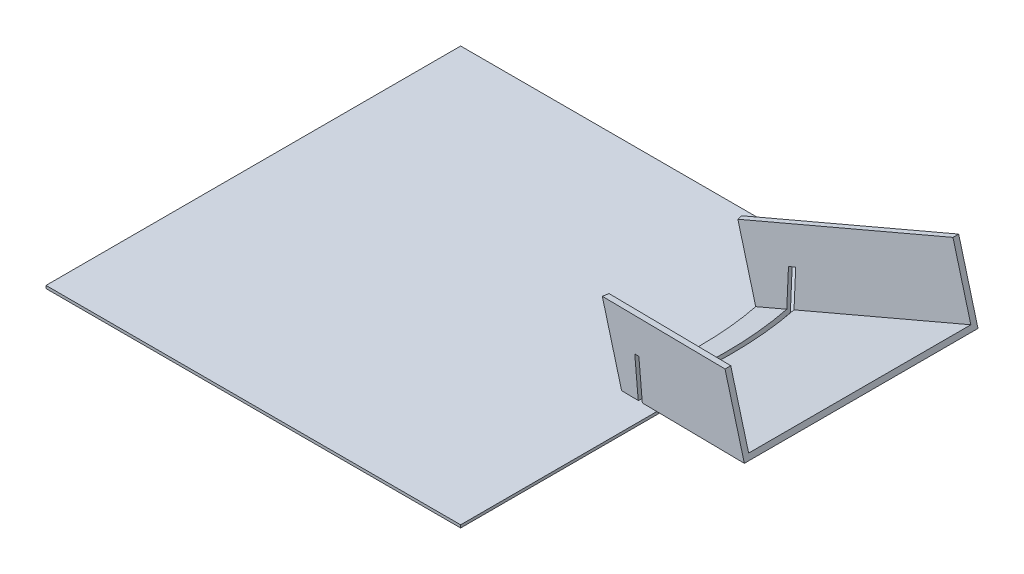
SolidWorks part; units mm, degrees
ref_plane "Front Plane" through (0, 0, 0) normal (0, 0, 1) x (1, 0, 0)
ref_plane "Top Plane" through (0, 0, 0) normal (0, 1, 0) x (1, 0, 0)
ref_plane "Right Plane" through (0, 0, 0) normal (1, 0, 0) x (0, 0, -1)
sketch "Sketch4" plane through (0, 0, 0) normal (0, 1, 0) x (1, 0, 0)
  line L1 (-75, 75) -> (75, 75)
  line L2 (-75, 75) -> (-75, -75)
  line L3 (-75, -75) -> (75, -75)
  line L4 (75, 75) -> (75, -75)
  point P4 (0, 75)
  point P6 (75, 0)
  dimension "D1" = 150
extrude "Boss-Extrude4" add sketch "Sketch4" along normal blind 1
ref_axis "Axis1" through (0, 0, -88.99) along (0, 0, 1)
ref_plane "Plane1" through (0, 0, 0) normal (0.2588, -0.9659, 0) x (0, 0, 1)
sketch "Sketch1" plane through (0, 0, 0) normal (-0.2588, 0.9659, 0) x (0.9659, 0.2588, 0)
  line L0 (0, 0) -> (150, 40.1924)
  line L1 (150, 40.1924) -> (150, -40.1924)
  line L2 (150, -40.1924) -> (0, 0)
  line L3 (150, 42.2629) -> (-0.5176, 1.9319)
  line L4 (150, -42.2629) -> (-0.5176, -1.9319)
  line L5 (-0.5176, 1.9319) -> (0, 0)
  line L6 (150, 42.2629) -> (150, 40.1924)
  line L7 (150, -42.2629) -> (150, -40.1924)
  line L8 (-0.5176, -1.9319) -> (0, 0)
  line L9 (57.2453, -78.7624) -> (62.5056, -85.9998) construction
  circle A0 centre (0, 0) radius 90
  circle A3 centre (0, 0) radius 100 construction
  circle A4 centre (0, 0) radius 97.368
  circle A5 centre (0, 0) radius 106.3152
  point P3 (150, 0)
  dimension "D3" = 180
  dimension "D4" = 200
  dimension "D1" = 150
  dimension "D2" = 30
  dimension "D6" = 2
  dimension "D7" = 2
extrude "Boss-Extrude5" add sketch "Sketch1" along normal blind 2 separate body contours A4 L2 A0 L0 | A4 L0 A0 L3 | A5 L0 A4 L3 | A5 L2 A4 L0 | A5 L4 A4 L2 | L4 A5 L2 L7 | L2 A5 L0 L1 | L0 A5 L3 L6 | A4 L4 A0 L2 region at (87.1517, 23.3522, -25.2113) region at (89.5078, 23.9835, 0) region at (87.1517, 23.3522, 25.2113) region at (94.7634, 25.3918, -27.3228) region at (97.3141, 26.0752, 0) region at (94.7634, 25.3918, 27.3228) region at (121.913, 32.6665, -34.8561) region at (124.4606, 33.3491, 0) region at (121.913, 32.6665, 34.8561)
extrude "Boss-Extrude6" add sketch "Sketch1<7>" along normal blind 25 from surface contours L0 A0 L3 L6 | L4 A0 L2 L7 | A4 L0 A0 L3 | A5 L0 A4 L3 | A5 L4 A4 L2 | A4 L4 A0 L2 region at (87.1517, 23.3522, -25.2113) region at (87.1517, 23.3522, 25.2113) region at (94.7634, 25.3918, -27.3228) region at (94.7634, 25.3918, 27.3228) region at (121.913, 32.6665, -34.8561) region at (121.913, 32.6665, 34.8561) starting at face at (114.5227, 32.7568, 0)
sketch "Sketch1<7>" plane through (0, 0, 0) normal (-0.2588, 0.9659, 0) x (0.9659, 0.2588, 0) same geometry as "Sketch1"
sketch "Sketch5" plane through (0, 0, 0) normal (0, 1, 0) x (1, 0, 0)
  circle A0 centre (0, 0) radius 98.9
  circle A1 centre (0, 0) radius 101.1
  dimension "D1" = 197.8
  dimension "D2" = 202.2
ref_axis "Axis4" through (0, 68.148, 0) along (0, -1, 0)
sketch "Sketch8" plane through (0, 0, 0) normal (0.2588, -0.9659, 0) x (-0.9659, -0.2588, 0)
  circle A0 centre (0, 0) radius 98.9
  circle A1 centre (0, 0) radius 101.1
extrude "Cut-Extrude4" cut sketch "Sketch8" along direction (0, -1, 0) on the side against the normal blind 15
equation "\"slope_angle\"= 15deg"
equation "\"wall_angle\"= 30deg"
equation "\"gate_radius\"= 100mm"
equation "\"gate_thickness\"= 2mm"
equation "\"slot_width\" = 1.1 * \"gate_thickness\""
equation "\"gate_angle\"= 30deg"
equation "\"wall_thickness\"= 2mm"
equation "\"D6@Sketch1\"=\"wall_thickness\""
equation "\"D7@Sketch1\"=2mm"
equation "\"wall_hieght\"= 25mm"
equation "\"D1@Boss-Extrude6\"=\"wall_hieght\""
equation "\"D1@Boss-Extrude5\"=\"wall_thickness\""
equation "\"slot_height\"= 15mm"
equation "\"D1@Sketch5\"=\"gate_radius\"*2 -\"slot_width\""
equation "\"D2@Sketch5\"=\"gate_radius\"*2 +\"slot_width\""
equation "\"D1@Cut-Extrude4\"=\"slot_height\""
equation "\"D4@Sketch1\"=2 *\"gate_radius\""
equation "\"gate_cross_width\"= 10mm"
equation "\"slot_cross_width\"= 1.1 * \"gate_cross_width\""
